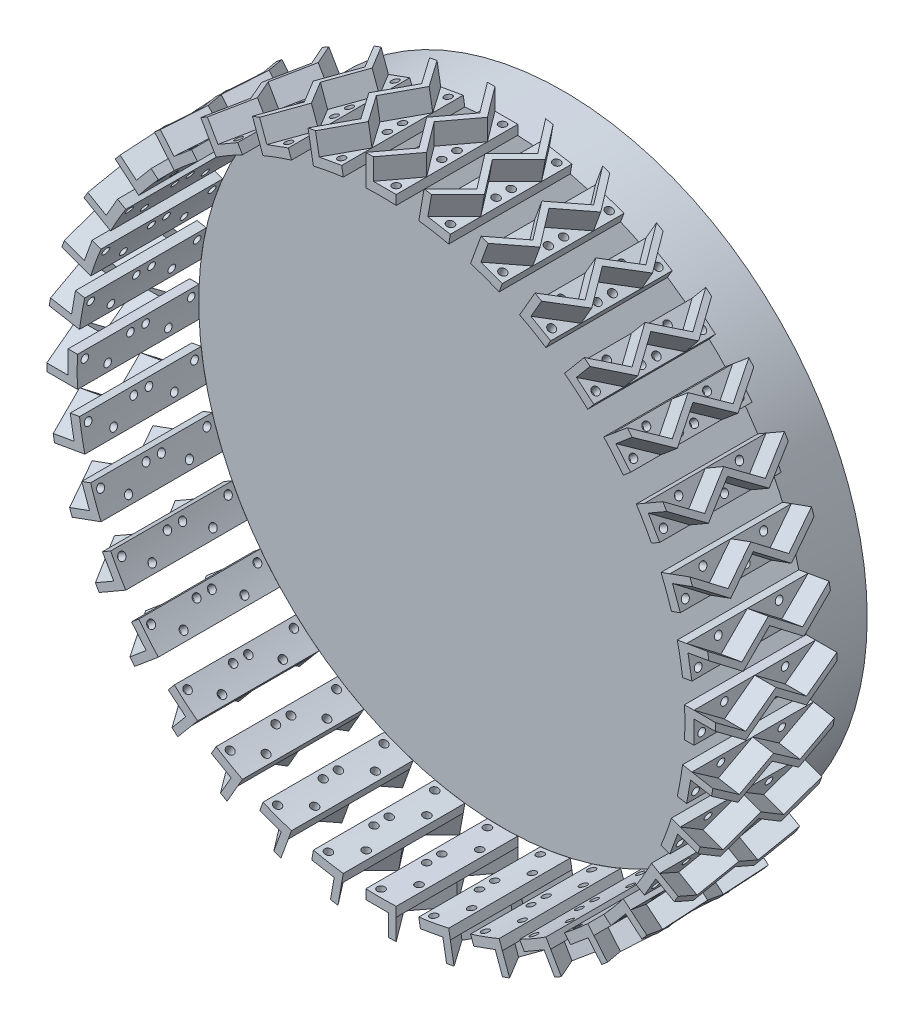
SolidWorks part; units mm, degrees
material "Polyetheretherketone (PEEK)"
ref_plane "Front Plane" through (0, 0, 0) normal (0, 0, 1) x (1, 0, 0)
ref_plane "Top Plane" through (0, 0, 0) normal (0, 1, 0) x (1, 0, 0)
ref_plane "Right Plane" through (0, 0, 0) normal (1, 0, 0) x (0, 0, -1)
sketch "Sketch1" plane through (0, 0, 0) normal (0, 0, 1) x (1, 0, 0)
  circle A0 centre (0, 0) radius 127
  dimension "D1" = 254
extrude "Boss-Extrude1" add sketch "Sketch1" along normal blind 50.8
ref_plane "Plane1" through (139.7, 0, 0) normal (1, 0, 0) x (0, 0, -1)
sketch "Sketch2" plane through (139.7, 0, 0) normal (1, 0, 0) x (0, 0, -1)
  line L0 (0, 0) -> (-25.4, 0)
  line L1 (0, 6.35) -> (-25.4, 6.35)
  line L2 (0, -6.35) -> (-25.4, -6.35)
  line L3 (-25.4, 0) -> (-25.4, -6.35)
  line L4 (0, 6.35) -> (0, -6.35)
  line L5 (-25.4, 6.35) -> (-12.7, -3.175)
  line L6 (-12.7, -3.175) -> (0, 6.35)
  line L7 (-25.4, 3.175) -> (-12.7, -6.35)
  line L8 (-12.7, -6.35) -> (0, 3.175)
  line L9 (-25.4, 6.35) -> (-25.4, 0)
  circle A0 centre (-22.225, -3.175) radius 1.5875
  circle A1 centre (-12.7, 3.175) radius 1.5875
  circle A2 centre (-3.175, -3.175) radius 1.5875
  dimension "D6" = 3.175
  dimension "D1" = 25.4
  dimension "D4" = 3.175
  dimension "D5" = 3.175
  dimension "D7" = 3.175
  dimension "D8" = 3.175
  dimension "D9" = 3.175
  dimension "D2" = 6.35
  dimension "D3" = 6.35
extrude "Boss-Extrude2" add sketch "Sketch2" against normal blind 15.24 separate body contours L8 L2 L4 L0 A2 | L8 L0 L4 | L0 L6 L1 L5 A1 | L5 L6 L0 | L7 L0 L3 L2 A0 | L7 L9 L0 | L7 L8 L0 L6 L5 | L5 L9 L7 L0 | L0 L8 L4 L6 region at (139.7, -3.7956, 4.8298) region at (139.7, 1.0583, 1.4111) region at (139.7, -3.0303, 8.5752) region at (139.7, 2.4694, 3.2926) region at (139.7, -1.0583, 12.7) region at (139.7, 0.2618, 12.7) region at (139.7, -3.7956, 20.5702) region at (139.7, 2.4694, 22.1074) region at (139.7, 1.0583, 23.9889)
extrude "Cut-Extrude1" cut sketch "Sketch2<4>" against normal blind 8.89 contours L8 L2 L4 L0 A2 | L8 L0 L4 | L0 L6 L1 L5 A1 | L7 L9 L0 | L5 L6 L0 | L7 L0 L3 L2 A0 region at (139.7, -3.7956, 4.8298) region at (139.7, 1.0583, 1.4111) region at (139.7, -1.0583, 12.7) region at (139.7, 0.2618, 12.7) region at (139.7, -3.7956, 20.5702) region at (139.7, 1.0583, 23.9889)
sketch "Sketch2<4>" plane through (139.7, 0, 0) normal (1, 0, 0) x (0, 0, -1) same geometry as "Sketch2"
pattern_linear "LPattern1" count 2 spacing 25.4 along (0, 0, 1) of bodies 105
combine bodies "Combine1" operation type add bodies to combine 106 105
extrude "Cut-Extrude2" cut sketch "Sketch1<2>" along normal blind 101.6
sketch "Sketch1<2>" plane through (0, 0, 0) normal (0, 0, 1) x (1, 0, 0) same geometry as "Sketch1"
extrude "Boss-Extrude3" add sketch "Sketch1<3>" against normal blind 25.4 separate body
sketch "Sketch1<3>" plane through (0, 0, 0) normal (0, 0, 1) x (1, 0, 0) same geometry as "Sketch1"
pattern_circular "CirPattern1" count 36 over 360 about axis through (0, 0, 0) along (0, 0, 1) of bodies 108
